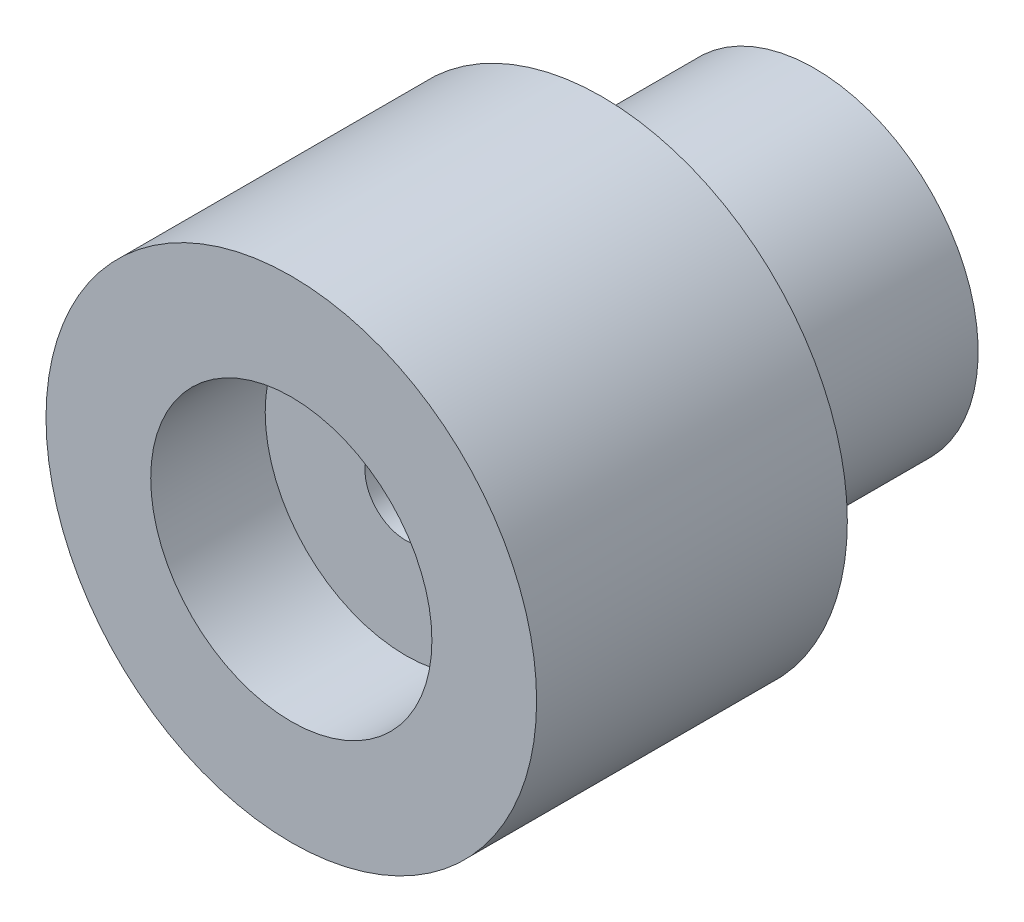
SolidWorks part; units mm, degrees
ref_plane "Front Plane" through (0, 0, 0) normal (0, 0, 1) x (1, 0, 0)
ref_plane "Top Plane" through (0, 0, 0) normal (0, 1, 0) x (1, 0, 0)
ref_plane "Right Plane" through (0, 0, 0) normal (1, 0, 0) x (0, 0, -1)
sketch "Sketch1" plane through (0, 0, 0) normal (0, 0, 1) x (1, 0, 0)
  circle A0 centre (0, 0) radius 15
extrude "Boss-Extrude1" add sketch "Sketch1" along normal blind 19
sketch "Sketch2" plane through (0, 0, 0) normal (0, 0, -1) x (-1, 0, 0)
  circle A0 centre (0, 0) radius 10
extrude "Boss-Extrude2" add sketch "Sketch2" along normal blind 13
sketch "Sketch3" plane through (0, 0, 19) normal (0, 0, 1) x (1, 0, 0)
  circle A0 centre (0, 0) radius 8.5968
extrude "Cut-Extrude1" cut sketch "Sketch3" against normal blind 7
sketch "Sketch4" plane through (0, 0, 12) normal (0, 0, 1) x (1, 0, 0)
  circle A0 centre (0, 0) radius 2.5
extrude "Cut-Extrude2" cut sketch "Sketch4" against normal blind 100
sketch "Sketch5" plane through (0, 0, -13) normal (0, 0, -1) x (-1, 0, 0)
  circle A0 centre (0, 0) radius 5.25
extrude "Cut-Extrude3" cut sketch "Sketch5" against normal blind 13
sketch "Sketch6" plane through (0, 0, -13) normal (0, 0, -1) x (-1, 0, 0)
  line L1 (3.7682, 2) -> (6.2434, 2)
  line L2 (3.7682, 2) -> (3.7682, -2)
  line L3 (3.7682, -2) -> (6.2434, -2)
  line L4 (6.2434, 2) -> (6.2434, -2)
  dimension "D1" = 4
  dimension "D2" = 2
extrude "Cut-Extrude4" cut sketch "Sketch6" against normal blind 7
